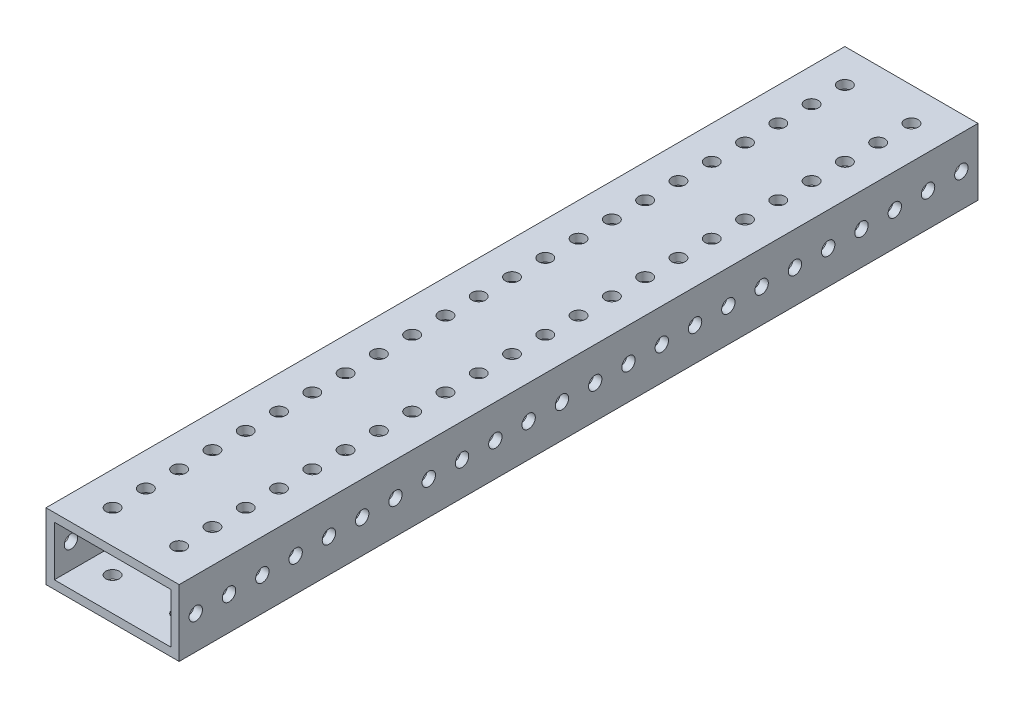
SolidWorks part; units mm, degrees
material "6061-T6 (SS)"
ref_plane "Front Plane" through (0, 0, 0) normal (0, 0, 1) x (1, 0, 0)
ref_plane "Top Plane" through (0, 0, 0) normal (0, 1, 0) x (1, 0, 0)
ref_plane "Right Plane" through (0, 0, 0) normal (1, 0, 0) x (0, 0, -1)
sketch "Sketch1" plane through (0, 0, 0) normal (0, 0, 1) x (1, 0, 0)
  line L0 (-22.225, 9.525) -> (22.225, 9.525)
  line L1 (-25.4, 12.7) -> (25.4, 12.7)
  line L2 (-25.4, 12.7) -> (-25.4, -12.7)
  line L3 (-25.4, -12.7) -> (25.4, -12.7)
  line L4 (25.4, 12.7) -> (25.4, -12.7)
  line L5 (22.225, 9.525) -> (22.225, -9.525)
  line L6 (-22.225, -9.525) -> (22.225, -9.525)
  line L7 (-22.225, 9.525) -> (-22.225, -9.525)
  line L8 (-25.4, 12.7) -> (25.4, -12.7) construction
  line L9 (25.4, 12.7) -> (-25.4, -12.7) construction
  point P5 (0, 0)
  dimension "D1" = 50.8
  dimension "D2" = 25.4
  dimension "D3" = 3.175
extrude "Boss-Extrude1" add sketch "Sketch1" along normal mid plane 368.3
sketch "Sketch5" plane through (-25.4, 0, 0) normal (-1, 0, 0) x (0, 0, 1)
  line L0 (184.15, -12.7) -> (-184.15, -12.7) construction
  line L1 (-184.15, 12.7) -> (-120.65, 12.7)
  line L2 (-184.15, 12.7) -> (-184.15, -12.7)
  line L3 (-184.15, -12.7) -> (-120.65, -12.7)
  line L4 (-120.65, 12.7) -> (-120.65, -12.7)
  dimension "D1" = 63.5
sketch "Sketch6" plane through (25.4, 0, 0) normal (1, 0, 0) x (0, 0, -1)
  line L0 (-184.15, -12.7) -> (-184.15, 12.7) construction
  line L1 (-184.15, 12.7) -> (184.15, 12.7) construction
  circle A0 centre (-177.8, 0) radius 2.5527
  circle A1 centre (-165.1, 0) radius 2.5527
  circle A2 centre (-152.4, 0) radius 2.5527
  circle A3 centre (-139.7, 0) radius 2.5527
  circle A4 centre (-127, 0) radius 2.5527
  circle A5 centre (-114.3, 0) radius 2.5527
  circle A6 centre (-101.6, 0) radius 2.5527
  circle A7 centre (-88.9, 0) radius 2.5527
  circle A8 centre (-76.2, 0) radius 2.5527
  circle A9 centre (-63.5, 0) radius 2.5527
  circle A10 centre (-50.8, 0) radius 2.5527
  circle A11 centre (-38.1, 0) radius 2.5527
  circle A12 centre (-25.4, 0) radius 2.5527
  circle A13 centre (-12.7, 0) radius 2.5527
  circle A14 centre (0, 0) radius 2.5527
  circle A15 centre (12.7, 0) radius 2.5527
  circle A16 centre (25.4, 0) radius 2.5527
  circle A17 centre (38.1, 0) radius 2.5527
  circle A18 centre (50.8, 0) radius 2.5527
  circle A19 centre (63.5, 0) radius 2.5527
  circle A20 centre (76.2, 0) radius 2.5527
  circle A21 centre (88.9, 0) radius 2.5527
  circle A22 centre (101.6, 0) radius 2.5527
  circle A23 centre (114.3, 0) radius 2.5527
  circle A24 centre (127, 0) radius 2.5527 construction
  circle A25 centre (139.7, 0) radius 2.5527 construction
  circle A26 centre (152.4, 0) radius 2.5527 construction
  circle A27 centre (165.1, 0) radius 2.5527 construction
  circle A28 centre (177.8, 0) radius 2.5527 construction
  dimension "D1" = 6.35
  dimension "D2" = 12.7
  dimension "D3" = 5.1054
  dimension "D4" = 29
extrude "Cut-Extrude5" cut sketch "Sketch6" against normal through all
extrude "Cut-Extrude6" cut sketch "Sketch5" against normal through all
sketch "Sketch2" plane through (0, 12.7, 0) normal (0, 1, 0) x (1, 0, 0)
  line L0 (25.4, -184.15) -> (-25.4, -184.15) construction
  line L1 (-25.4, -184.15) -> (-25.4, 120.65) construction
  line L4 (25.4, 184.15) -> (-25.4, 184.15) construction
  circle A0 centre (12.7, -171.45) radius 2.5527
  circle A1 centre (25.4, -171.45) radius 2.5527 construction
  circle A2 centre (-12.7, -171.45) radius 2.5527
  circle A3 centre (-12.7, -158.75) radius 2.5527
  circle A4 centre (12.7, -158.75) radius 2.5527 construction
  circle A5 centre (25.4, -158.75) radius 2.5527 construction
  circle A6 centre (-12.7, -146.05) radius 2.5527
  circle A7 centre (12.7, -146.05) radius 2.5527 construction
  circle A8 centre (25.4, -146.05) radius 2.5527 construction
  circle A9 centre (-12.7, -133.35) radius 2.5527
  circle A10 centre (12.7, -133.35) radius 2.5527 construction
  circle A11 centre (25.4, -133.35) radius 2.5527 construction
  circle A12 centre (-12.7, -120.65) radius 2.5527
  circle A13 centre (12.7, -120.65) radius 2.5527 construction
  circle A14 centre (25.4, -120.65) radius 2.5527 construction
  circle A15 centre (-12.7, -107.95) radius 2.5527
  circle A16 centre (12.7, -107.95) radius 2.5527 construction
  circle A17 centre (25.4, -107.95) radius 2.5527 construction
  circle A18 centre (-12.7, -95.25) radius 2.5527
  circle A19 centre (12.7, -95.25) radius 2.5527 construction
  circle A20 centre (25.4, -95.25) radius 2.5527 construction
  circle A21 centre (-12.7, -82.55) radius 2.5527
  circle A22 centre (12.7, -82.55) radius 2.5527 construction
  circle A23 centre (25.4, -82.55) radius 2.5527 construction
  circle A24 centre (-12.7, -69.85) radius 2.5527
  circle A25 centre (12.7, -69.85) radius 2.5527 construction
  circle A26 centre (25.4, -69.85) radius 2.5527 construction
  circle A27 centre (-12.7, -57.15) radius 2.5527
  circle A28 centre (12.7, -57.15) radius 2.5527 construction
  circle A29 centre (25.4, -57.15) radius 2.5527 construction
  circle A30 centre (-12.7, -44.45) radius 2.5527
  circle A31 centre (12.7, -44.45) radius 2.5527 construction
  circle A32 centre (25.4, -44.45) radius 2.5527 construction
  circle A33 centre (-12.7, -31.75) radius 2.5527
  circle A34 centre (12.7, -31.75) radius 2.5527 construction
  circle A35 centre (25.4, -31.75) radius 2.5527 construction
  circle A36 centre (-12.7, -19.05) radius 2.5527
  circle A37 centre (12.7, -19.05) radius 2.5527 construction
  circle A38 centre (25.4, -19.05) radius 2.5527 construction
  circle A39 centre (-12.7, -6.35) radius 2.5527
  circle A40 centre (12.7, -6.35) radius 2.5527 construction
  circle A41 centre (25.4, -6.35) radius 2.5527 construction
  circle A42 centre (-12.7, 6.35) radius 2.5527
  circle A43 centre (12.7, 6.35) radius 2.5527 construction
  circle A44 centre (25.4, 6.35) radius 2.5527 construction
  circle A45 centre (-12.7, 19.05) radius 2.5527
  circle A46 centre (12.7, 19.05) radius 2.5527 construction
  circle A47 centre (25.4, 19.05) radius 2.5527 construction
  circle A48 centre (-12.7, 31.75) radius 2.5527
  circle A49 centre (12.7, 31.75) radius 2.5527 construction
  circle A50 centre (25.4, 31.75) radius 2.5527 construction
  circle A51 centre (-12.7, 44.45) radius 2.5527
  circle A52 centre (12.7, 44.45) radius 2.5527 construction
  circle A53 centre (25.4, 44.45) radius 2.5527 construction
  circle A54 centre (-12.7, 57.15) radius 2.5527
  circle A55 centre (12.7, 57.15) radius 2.5527 construction
  circle A56 centre (25.4, 57.15) radius 2.5527 construction
  circle A57 centre (-12.7, 69.85) radius 2.5527
  circle A58 centre (12.7, 69.85) radius 2.5527 construction
  circle A59 centre (25.4, 69.85) radius 2.5527 construction
  circle A60 centre (-12.7, 82.55) radius 2.5527
  circle A61 centre (12.7, 82.55) radius 2.5527 construction
  circle A62 centre (25.4, 82.55) radius 2.5527 construction
  circle A63 centre (-12.7, 95.25) radius 2.5527
  circle A64 centre (12.7, 95.25) radius 2.5527 construction
  circle A65 centre (25.4, 95.25) radius 2.5527 construction
  circle A66 centre (-12.7, 107.95) radius 2.5527
  circle A67 centre (12.7, 107.95) radius 2.5527 construction
  circle A68 centre (25.4, 107.95) radius 2.5527 construction
  circle A69 centre (-12.7, 120.65) radius 2.5527 construction
  circle A70 centre (12.7, 120.65) radius 2.5527 construction
  circle A71 centre (25.4, 120.65) radius 2.5527 construction
  circle A72 centre (-12.7, 133.35) radius 2.5527 construction
  circle A73 centre (12.7, 133.35) radius 2.5527 construction
  circle A74 centre (25.4, 133.35) radius 2.5527 construction
  circle A75 centre (-12.7, 146.05) radius 2.5527
  circle A76 centre (12.7, 146.05) radius 2.5527 construction
  circle A77 centre (25.4, 146.05) radius 2.5527 construction
  circle A78 centre (-12.7, 158.75) radius 2.5527
  circle A79 centre (12.7, 158.75) radius 2.5527 construction
  circle A80 centre (25.4, 158.75) radius 2.5527 construction
  circle A81 centre (-12.7, 171.45) radius 2.5527
  circle A82 centre (12.7, 171.45) radius 2.5527 construction
  circle A83 centre (25.4, 171.45) radius 2.5527 construction
  circle A84 centre (-12.7, 184.15) radius 2.5527 construction
  circle A85 centre (12.7, 184.15) radius 2.5527 construction
  circle A86 centre (25.4, 184.15) radius 2.5527 construction
  circle A87 centre (-12.7, 196.85) radius 2.5527
  circle A88 centre (12.7, 196.85) radius 2.5527 construction
  circle A89 centre (25.4, 196.85) radius 2.5527 construction
  circle A90 centre (-12.7, 209.55) radius 2.5527
  circle A91 centre (12.7, 209.55) radius 2.5527 construction
  circle A92 centre (25.4, 209.55) radius 2.5527 construction
  circle A93 centre (-12.7, 222.25) radius 2.5527
  circle A94 centre (12.7, 222.25) radius 2.5527 construction
  circle A95 centre (25.4, 222.25) radius 2.5527 construction
  circle A96 centre (-12.7, 234.95) radius 2.5527
  circle A97 centre (12.7, 234.95) radius 2.5527 construction
  circle A98 centre (25.4, 234.95) radius 2.5527 construction
  circle A99 centre (-12.7, 247.65) radius 2.5527
  circle A100 centre (12.7, 247.65) radius 2.5527 construction
  circle A101 centre (25.4, 247.65) radius 2.5527 construction
  circle A108 centre (-12.7, 273.05) radius 2.5527 [skipped]
  circle A109 centre (12.7, 273.05) radius 2.5527 [skipped]
  circle A110 centre (25.4, 273.05) radius 2.5527 [skipped]
  circle A111 centre (-12.7, 260.35) radius 2.5527 [skipped]
  circle A112 centre (12.7, 260.35) radius 2.5527 [skipped]
  circle A113 centre (25.4, 260.35) radius 2.5527 [skipped]
  circle A114 centre (25.4, 260.35) radius 2.5527 construction
  circle A115 centre (12.7, 260.35) radius 2.5527 construction
  circle A116 centre (-12.7, 260.35) radius 2.5527
  circle A117 centre (25.4, 273.05) radius 2.5527 construction
  circle A118 centre (12.7, 273.05) radius 2.5527 construction
  circle A119 centre (-12.7, 273.05) radius 2.5527
  circle A120 centre (25.4, 285.75) radius 2.5527 construction
  circle A121 centre (12.7, 285.75) radius 2.5527 construction
  circle A122 centre (-12.7, 285.75) radius 2.5527
  circle A123 centre (25.4, 298.45) radius 2.5527 construction
  circle A124 centre (12.7, 298.45) radius 2.5527 construction
  circle A125 centre (-12.7, 298.45) radius 2.5527
  circle A126 centre (25.4, 311.15) radius 2.5527 construction
  circle A127 centre (12.7, 311.15) radius 2.5527 construction
  circle A128 centre (-12.7, 311.15) radius 2.5527
  circle A129 centre (25.4, 323.85) radius 2.5527 construction
  circle A130 centre (12.7, 323.85) radius 2.5527 construction
  circle A131 centre (-12.7, 323.85) radius 2.5527
  circle A132 centre (25.4, 336.55) radius 2.5527 construction
  circle A133 centre (12.7, 336.55) radius 2.5527 construction
  circle A134 centre (-12.7, 336.55) radius 2.5527
  circle A135 centre (25.4, 349.25) radius 2.5527 construction
  circle A136 centre (12.7, 349.25) radius 2.5527 construction
  circle A137 centre (-12.7, 349.25) radius 2.5527
  circle A138 centre (25.4, 361.95) radius 2.5527 construction
  circle A139 centre (12.7, 361.95) radius 2.5527 construction
  circle A140 centre (-12.7, 361.95) radius 2.5527
  circle A141 centre (25.4, 374.65) radius 2.5527 construction
  circle A142 centre (12.7, 374.65) radius 2.5527 construction
  circle A143 centre (-12.7, 374.65) radius 2.5527
  circle A144 centre (25.4, 387.35) radius 2.5527 construction
  circle A145 centre (12.7, 387.35) radius 2.5527 construction
  circle A146 centre (-12.7, 387.35) radius 2.5527
  circle A147 centre (25.4, 400.05) radius 2.5527 construction
  circle A148 centre (12.7, 400.05) radius 2.5527 construction
  circle A149 centre (-12.7, 400.05) radius 2.5527
  circle A150 centre (25.4, 412.75) radius 2.5527 construction
  circle A151 centre (12.7, 412.75) radius 2.5527 construction
  circle A152 centre (-12.7, 412.75) radius 2.5527
  circle A153 centre (12.7, -158.75) radius 2.5527
  circle A154 centre (12.7, -146.05) radius 2.5527
  circle A155 centre (12.7, -133.35) radius 2.5527
  circle A156 centre (12.7, -120.65) radius 2.5527
  circle A157 centre (12.7, -107.95) radius 2.5527
  circle A158 centre (12.7, -95.25) radius 2.5527
  circle A159 centre (12.7, -82.55) radius 2.5527
  circle A160 centre (12.7, -69.85) radius 2.5527
  circle A161 centre (12.7, -57.15) radius 2.5527
  circle A162 centre (12.7, -44.45) radius 2.5527
  circle A163 centre (12.7, -31.75) radius 2.5527
  circle A164 centre (12.7, -19.05) radius 2.5527
  circle A165 centre (12.7, -6.35) radius 2.5527
  circle A166 centre (12.7, 6.35) radius 2.5527
  circle A167 centre (12.7, 19.05) radius 2.5527
  circle A168 centre (12.7, 31.75) radius 2.5527
  circle A169 centre (12.7, 44.45) radius 2.5527
  circle A170 centre (12.7, 57.15) radius 2.5527
  circle A171 centre (12.7, 69.85) radius 2.5527
  circle A172 centre (12.7, 82.55) radius 2.5527
  circle A173 centre (12.7, 95.25) radius 2.5527
  circle A174 centre (12.7, 107.95) radius 2.5527
  circle A175 centre (12.7, 120.65) radius 2.5527 construction
  circle A176 centre (12.7, 133.35) radius 2.5527 construction
  circle A177 centre (12.7, 146.05) radius 2.5527
  circle A178 centre (12.7, 158.75) radius 2.5527
  circle A179 centre (12.7, 171.45) radius 2.5527
  circle A180 centre (12.7, 184.15) radius 2.5527 construction
  circle A181 centre (12.7, 196.85) radius 2.5527
  circle A182 centre (12.7, 209.55) radius 2.5527
  circle A183 centre (12.7, 222.25) radius 2.5527
  circle A184 centre (12.7, 234.95) radius 2.5527
  circle A185 centre (12.7, 247.65) radius 2.5527
  circle A186 centre (12.7, 260.35) radius 2.5527
  circle A187 centre (12.7, 273.05) radius 2.5527
  circle A188 centre (12.7, 285.75) radius 2.5527
  circle A189 centre (12.7, 298.45) radius 2.5527
  circle A190 centre (12.7, 311.15) radius 2.5527
  circle A191 centre (12.7, 323.85) radius 2.5527
  circle A192 centre (12.7, 336.55) radius 2.5527
  circle A193 centre (12.7, 349.25) radius 2.5527
  circle A194 centre (12.7, 361.95) radius 2.5527
  circle A195 centre (12.7, 374.65) radius 2.5527
  circle A196 centre (12.7, 387.35) radius 2.5527
  circle A197 centre (12.7, 400.05) radius 2.5527
  circle A198 centre (12.7, 412.75) radius 2.5527
  circle A199 centre (12.7, 425.45) radius 2.5527
  circle A200 centre (12.7, 438.15) radius 2.5527
  circle A201 centre (12.7, 450.85) radius 2.5527
  dimension "D2" = 5.1054
  dimension "D4" = 50
  dimension "D9" = 12.7
  dimension "D10" = 12.7
  dimension "D11" = 12.7
  dimension "D1" = 12.7
  dimension "D3" = 38.1
  dimension "D6" = 12.7
  dimension "D7" = 63.5
  dimension "D5" = 36
  dimension "D8" = 14
extrude "Cut-Extrude1" cut sketch "Sketch2" against normal through all
